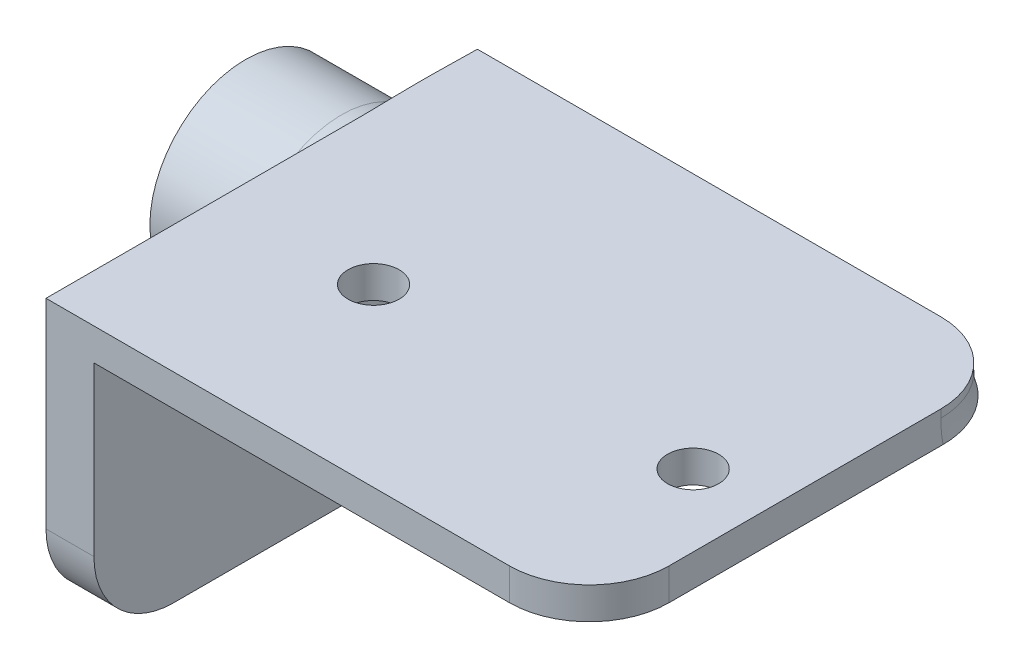
SolidWorks part; units mm, degrees
ref_plane "Alzado" through (0, 0, 0) normal (0, 0, 1) x (1, 0, 0)
ref_plane "Planta" through (0, 0, 0) normal (0, 1, 0) x (1, 0, 0)
ref_plane "Vista lateral" through (0, 0, 0) normal (1, 0, 0) x (0, 0, -1)
sketch "Croquis1" plane through (0, 0, 0) normal (0, 1, 0) x (1, 0, 0)
  line L1 (0, 0) -> (34, 0)
  line L2 (0, 0) -> (0, -20)
  line L3 (0, -20) -> (34, -20)
  line L4 (34, 0) -> (34, -20)
  dimension "D1" = 34
  dimension "D2" = 20
extrude "Saliente-Extruir1" add sketch "Croquis1" along normal blind 3.5
sketch "Croquis2" plane through (0, 3.5, 0) normal (0, 1, 0) x (1, 0, 0)
  line L0 (0, 0) -> (0, -20) construction
  line L1 (0, -20) -> (34, -20) construction
  circle A0 centre (9.5, -9) radius 1.6
  circle A1 centre (29.5, -9) radius 1.6
  dimension "D1" = 3.2
  dimension "D2" = 3.2
  dimension "D3" = 20
  dimension "D4" = 9.5
  dimension "D5" = 11
extrude "Cortar-Extruir1" cut sketch "Croquis2" against normal up to surface (3.5 mm away) up to face at (17, 0, 10)
sketch "Croquis3" plane through (0, 0, 0) normal (0, -1, 0) x (1, 0, 0)
  line L0 (0, 20) -> (34, 20) construction
  line L1 (0, 0) -> (3, 0)
  line L2 (0, 0) -> (0, 20)
  line L3 (0, 20) -> (3, 20)
  line L4 (3, 0) -> (3, 20)
  dimension "D1" = 3
extrude "Saliente-Extruir2" add sketch "Croquis3" along normal blind 20
sketch "Croquis4" plane through (0, 0, 0) normal (0, 0, -1) x (-1, 0, 0)
  line L0 (-3, -20) -> (-3, 0) construction
  line L1 (-3, -1.5) -> (0, -1.5)
  line L2 (-3, -1.5) -> (-3, -15.5)
  line L3 (-3, -15.5) -> (0, -15.5)
  line L4 (0, -1.5) -> (0, -15.5)
  line L5 (0, 3.5) -> (0, -20) construction
  line L6 (-34, 3.5) -> (0, 3.5) construction
  dimension "D1" = 14
  dimension "D2" = 5
extrude "Saliente-Extruir3" add sketch "Croquis4" along normal blind 10
sketch "Croquis5" plane through (0, 0, 0) normal (-1, 0, 0) x (0, 0, 1)
  line L0 (-10, -15.5) -> (0, -15.5) construction
  line L1 (0, 3.5) -> (0, -1.5) construction
  circle A0 centre (-3.5, -8.3) radius 6
  dimension "D1" = 12
  dimension "D2" = 7.2
  dimension "D3" = 3.5
extrude "Saliente-Extruir4" add sketch "Croquis5" along normal blind 11
sketch "Croquis6" plane through (-11, 0, 0) normal (-1, 0, 0) x (0, 0, 1)
  circle A0 centre (-3.5, -8.3) radius 1.5
  dimension "D1" = 3
extrude "Cortar-Extruir2" cut sketch "Croquis6" against normal up to surface (14 mm away) up to face at (3, -9.25, 2.5)
sketch "Croquis7" plane through (3, 0, 0) normal (1, 0, 0) x (0, 0, -1)
  line L0 (10, -1.5) -> (10, -15.5) construction
  line L1 (7.1, -12.9) -> (0.8, -12.9)
  line L2 (7.1, -12.9) -> (7.1, -4.6)
  line L3 (7.1, -4.6) -> (0.8, -4.6)
  line L4 (0.8, -12.9) -> (0.8, -4.6)
  line L5 (10, -15.5) -> (0, -15.5) construction
  dimension "D1" = 8.3
  dimension "D2" = 6.3
  dimension "D3" = 2.9
  dimension "D4" = 2.6
extrude "Cortar-Extruir3" cut sketch "Croquis7" against normal blind 6.4
sketch "Croquis8" plane through (-11, 0, 0) normal (-1, 0, 0) x (0, 0, 1)
  circle A0 centre (-3.5, -8.3) radius 4.2
  dimension "D1" = 8.4
extrude "Cortar-Extruir4" cut sketch "Croquis8" against normal blind 6.3
fillet "Redondeo1" radius 1 1 edges at (-3.4, -8.3, -5)
sketch "Croquis9" plane through (3, 0, 0) normal (1, 0, 0) x (0, 0, -1)
  line L0 (-20, -20) -> (-20, 0) construction
  line L1 (0, -20) -> (-20, -20)
  line L2 (0, -20) -> (0, -15.5)
  line L3 (0, -15.5) -> (-20, -15.5)
  line L4 (-20, -20) -> (-20, -15.5)
  line L5 (10, -15.5) -> (0, -15.5) construction
extrude "Cortar-Extruir5" cut sketch "Croquis9" against normal up to surface (3 mm away) up to face at (0, -8.3, -9.5)
sketch "Croquis11" plane through (0, 0, 0) normal (0, 0, -1) x (-1, 0, 0)
  line L6 (-3, -1.5) -> (0, -1.5)
  line L7 (0, -1.5) -> (0, 3.5)
  line L8 (0, 3.5) -> (-34, 3.5)
  line L9 (-34, 3.5) -> (-34, 0)
  line L10 (-34, 0) -> (-3, 0)
  line L11 (-3, 0) -> (-3, -1.5)
  line L12 (-3, -1.5) -> (0, -1.5)
  line L13 (0, -1.5) -> (0, 3.5)
  line L14 (0, 3.5) -> (-34, 3.5)
  line L15 (-34, 3.5) -> (-34, 0)
  line L16 (-34, 0) -> (-3, 0)
  line L17 (-3, 0) -> (-3, -1.5)
  dimension "D1" = 0
extrude "Saliente-Extruir5" add sketch "Croquis11" along normal blind 7
fillet "Redondeo5" radius 3 1 edges at (1.5, -1.5, -7)
fillet "Redondeo6" radius 5 5 edges at (34, 0.7235, -7.1022) (34, 1.75, 20) (34, 2.5, -7) (1.5, -15.5, 20) (1.5, -15.5, -10)
sketch "Croquis12" plane through (0, 3.5, 0) normal (0, 1, 0) x (1, 0, 0)
  line L4 (0, -20) -> (29, -20)
  line L5 (34, -15) -> (34, 2)
  line L6 (29, 7) -> (0, 7)
  line L7 (0, 7) -> (0, -20)
  line L8 (0, -20) -> (29, -20)
  line L9 (34, -15) -> (34, 2)
  line L10 (29, 7) -> (0, 7)
  line L11 (0, 7) -> (0, -20)
  circle A0 centre (9.5, -9) radius 1.6 construction
  circle A1 centre (9.5, -9) radius 1.6
  arc A2 (29, -20) -> (34, -15) centre (29, -15) ccw
  arc A3 (34, 2) -> (29, 7) centre (29, 2) ccw
  arc A4 (29, -20) -> (34, -15) centre (29, -15) ccw
  arc A5 (34, 2) -> (29, 7) centre (29, 2) ccw
  circle A6 centre (29.5, -9) radius 1.6 construction
  circle A7 centre (29.5, -9) radius 1.6
  dimension "D1" = 0
extrude "Cortar-Extruir6" cut sketch "Croquis12" against normal blind 1.5
fillet "Redondeo7" radius 5 1 edges at (0, -8.3, -9.5)
